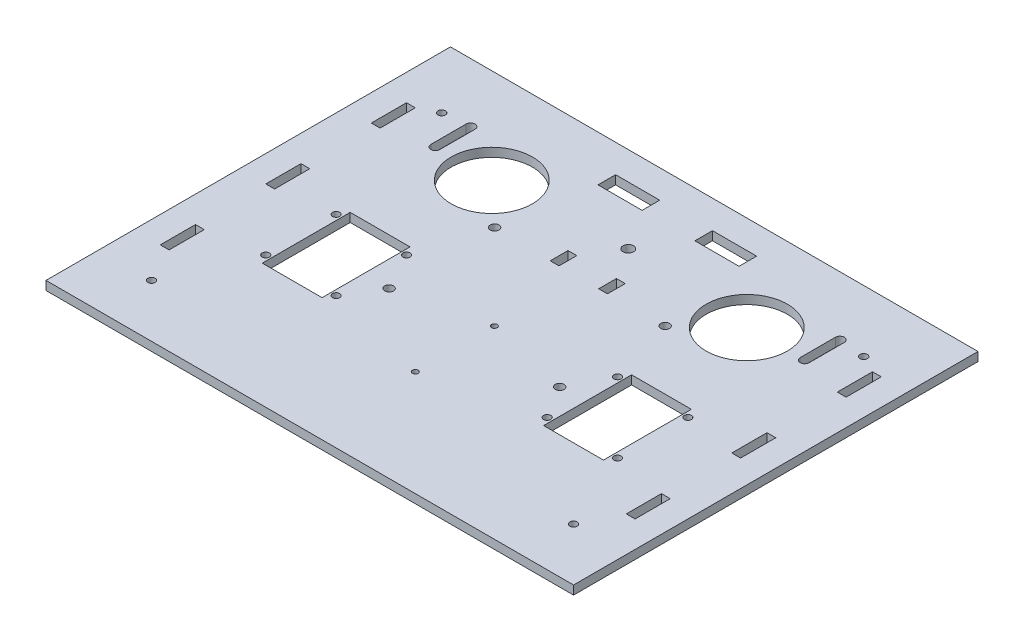
SolidWorks part; units mm, degrees
ref_plane "前基準面" through (0, 0, 0) normal (0, 0, 1) x (1, 0, 0)
ref_plane "上基準面" through (0, 0, 0) normal (0, 1, 0) x (1, 0, 0)
ref_plane "右基準面" through (0, 0, 0) normal (1, 0, 0) x (0, 0, -1)
sketch "草圖1" plane through (0, 0, 0) normal (0, 1, 0) x (1, 0, 0)
  line L0 (-130, 90) -> (130, 90) construction
  line L1 (-150, 100) -> (150, 100) construction
  line L2 (-150, 100) -> (-150, -100)
  line L3 (-150, -100) -> (150, -100) construction
  line L5 (0, 100) -> (0, -100) construction
  line L8 (-130, 100) -> (-110, 100) construction
  line L9 (-150, 100) -> (-150, -100) construction
  line L16 (-130, 100) -> (-130, -100) construction
  line L17 (-130, -100) -> (-110, -100) construction
  line L23 (-150, -100) -> (150, -100) construction
  line L26 (-150, -100) -> (-150, -120)
  line L29 (-150, -120) -> (150, -120)
  line L32 (150, -100) -> (150, -120)
  line L35 (-110, 100) -> (-110, -100) construction
  line L38 (-110, 100) -> (110, 100) construction
  line L41 (-110, 100) -> (-110, 80) construction
  line L50 (-110, 80) -> (110, 80) construction
  line L59 (110, 100) -> (110, 80) construction
  line L65 (-150, -100) -> (150, -100) construction
  line L68 (150, -100) -> (150, 100)
  line L70 (-150, 100) -> (150, 100) construction
  line L73 (-150, 100) -> (-150, 110)
  line L77 (110, 100) -> (130, 100) construction
  line L80 (110, 100) -> (110, -100) construction
  line L83 (110, -100) -> (130, -100) construction
  line L86 (130, 100) -> (130, -100) construction
  line L89 (110, -100) -> (-110, -100) construction
  line L92 (110, -100) -> (110, -80) construction
  line L93 (-150, 100) -> (150, 100) construction
  line L97 (-150, 110) -> (150, 110)
  line L98 (150, 100) -> (150, 110)
  line L108 (110, -80) -> (-110, -80) construction
  line L109 (-110, -100) -> (-110, -80) construction
  line L110 (130, -70) -> (135, -70)
  line L111 (-120, 100) -> (-120, -100) construction
  line L112 (-130, -90) -> (130, -90) construction
  line L113 (120, -100) -> (120, 100) construction
  line L114 (-130, 70) -> (-135, 70)
  line L115 (-130, 70) -> (-130, 50)
  line L116 (-130, 50) -> (-135, 50)
  line L117 (-135, 70) -> (-135, 50)
  line L118 (-130, 10) -> (-135, 10)
  line L119 (-130, 10) -> (-130, -10)
  line L120 (-130, -10) -> (-135, -10)
  line L121 (-135, 10) -> (-135, -10)
  line L122 (-130, -50) -> (-135, -50)
  line L123 (-130, -50) -> (-130, -70)
  line L124 (-130, -70) -> (-135, -70)
  line L125 (-135, -50) -> (-135, -70)
  line L126 (135, -50) -> (135, -70)
  line L127 (130, -50) -> (135, -50)
  line L128 (130, -50) -> (130, -70)
  line L129 (130, -10) -> (135, -10)
  line L130 (135, 10) -> (135, -10)
  line L131 (130, 10) -> (135, 10)
  line L132 (130, 10) -> (130, -10)
  line L133 (130, 50) -> (135, 50)
  line L134 (135, 70) -> (135, 50)
  line L135 (130, 70) -> (135, 70)
  line L136 (130, 70) -> (130, 50)
  circle A73 centre (-120, 75) radius 2.1
  circle A74 centre (120, 75) radius 2.1
  circle A75 centre (120, -90) radius 2.1
  circle A76 centre (-120, -90) radius 2.1
  point P6 (0, 0)
  point P9 (0, -80)
  point P23 (0, 0)
  point P24 (-140, 64.2857)
  point P44 (0, 0)
  point P47 (-140, 38.5714)
  point P54 (-140, 12.8571)
  point P61 (-140, -12.8571)
  point P71 (-140, -38.5714)
  point P78 (-140, -64.2857)
  dimension "D3" = 300
  dimension "D5" = 20
  dimension "D8" = 220
  dimension "D13" = 4.2
  dimension "D14" = 20
  dimension "D2" = 200
  dimension "D4" = 20
  dimension "D6" = 20
  dimension "D7" = 20
  dimension "D9" = 10
  dimension "D10" = 10
  dimension "D11" = 10
  dimension "D12" = 10
  dimension "D15" = 20
  dimension "D16" = 20
  dimension "D18" = 5
  dimension "D19" = 40
  dimension "D20" = 40
  dimension "D21" = 30
  dimension "D23" = 20
  dimension "D22" = 25
  dimension "D24" = 10
extrude "填料-伸長1" add sketch "草圖1" along normal blind 5
sketch "草圖2" plane through (0, 5, 0) normal (0, 1, 0) x (1, 0, 0)
  line L0 (0, 116.4556) -> (0, -113.9778) construction
  line L1 (115, 56) -> (30, 56) construction
  line L2 (-72.5, 98.5) -> (-72.5, 13.5) construction
  line L3 (-115, 56) -> (-30, 56) construction
  line L4 (72.5, 98.5) -> (72.5, 13.5) construction
  line L10 (7.5, -53.8861) -> (-7.5, -53.8861) construction
  line L15 (7.5, -53.8861) -> (7.5, 16.1139) construction
  line L16 (7.5, 16.1139) -> (-7.5, 16.1139) construction
  line L17 (-7.5, -53.8861) -> (-7.5, 16.1139) construction
  line L20 (-7.5, 16.1139) -> (7.5, 16.1139) construction
  line L35 (-110, 100) -> (-110, -100) construction
  line L36 (36, -46.3861) -> (-36, -46.3861) construction
  line L37 (36, -46.3861) -> (36, 63.6139) construction
  line L38 (36, 63.6139) -> (-36, 63.6139) construction
  line L39 (-36, -46.3861) -> (-36, 63.6139) construction
  line L40 (-105, 0) -> (-55, 0) construction
  line L41 (-105, 0) -> (-105, -50) construction
  line L42 (-55, 0) -> (-55, -50) construction
  line L43 (-97, 0) -> (-63, 0)
  line L46 (-97, 0) -> (-97, -50)
  line L49 (-97, -50) -> (-63, -50)
  line L60 (-7.5, -6.3861) -> (7.5, -6.3861)
  line L61 (-7.5, -6.3861) -> (-7.5, -31.3861)
  line L62 (-7.5, -31.3861) -> (7.5, -31.3861)
  line L63 (7.5, -6.3861) -> (7.5, -31.3861)
  line L64 (-63, 0) -> (-63, -50)
  line L67 (-105, -50) -> (-55, -50) construction
  line L72 (-150, 100) -> (150, 100) construction
  line L73 (-150, -100) -> (150, -100) construction
  line L74 (97, 0) -> (97, -50)
  line L75 (240, -51.3861) -> (-240, -51.3861) construction
  line L76 (240, -51.3861) -> (240, 28.6139) construction
  line L78 (-240, -51.3861) -> (-240, 28.6139) construction
  line L83 (0, -40.4951) -> (0, 39.5049) construction
  line L84 (-150, 100) -> (150, 100)
  line L85 (97, -50) -> (63, -50)
  line L86 (63, 0) -> (63, -50)
  line L87 (97, 0) -> (63, 0)
  line L88 (-7.5, -46.3861) -> (-7.5, -71.3861)
  line L89 (-7.5, -46.3861) -> (7.5, -46.3861)
  line L90 (7.5, -46.3861) -> (7.5, -71.3861)
  line L91 (-7.5, -71.3861) -> (7.5, -71.3861)
  line L92 (240, 28.6139) -> (-240, 28.6139) construction
  circle A0 centre (-72.5, 56) radius 42.5
  circle A1 centre (-72.5, 56) radius 22.1
  circle A2 centre (-87, 56) radius 2
  circle A3 centre (-58, 56) radius 2
  circle A4 centre (58, 56) radius 2
  circle A5 centre (87, 56) radius 2
  circle A6 centre (72.5, 56) radius 22.1
  circle A7 centre (72.5, 56) radius 42.5
  circle A11 centre (0, -41.3861) radius 1.25 construction
  circle A12 centre (0, 28.6139) radius 35 construction
  circle A13 centre (0, 3.6139) radius 1.25 construction
  circle A28 centre (60, -45) radius 2.05
  circle A36 centre (-100, -5) radius 2.05
  circle A37 centre (-60, -5) radius 2.05
  circle A38 centre (-100, -45) radius 2.05
  circle A39 centre (-60, -45) radius 2.05
  circle A40 centre (100, -45) radius 2.05
  circle A41 centre (60, -5) radius 2.05
  circle A42 centre (100, -5) radius 2.05
  circle A43 centre (0, -11.3861) radius 35 construction
  point P29 (0, 63.6139)
  point P46 (-7.5, -18.8861)
  point P57 (-7.5, -18.8861)
  point P68 (-36, -98.5061)
  point P69 (0, 53.9014)
  point P85 (-96.5, 66.7857)
  point P90 (-141.5, 66.7857)
  point P91 (-140, 13.2857)
  point P92 (-140, 68.2857)
  point P116 (0, -53.8861)
  point P142 (0, -51.3861)
  point P143 (0, 53.9014)
  dimension "D1" = 85
  dimension "D2" = 44.2
  dimension "D4" = 4
  dimension "D8" = 72
  dimension "D10" = 44
  dimension "D7" = 2
  dimension "D16" = 70
  dimension "D13" = 2.5
  dimension "D17" = 2
  dimension "D24" = 45
  dimension "D25" = 4.1
  dimension "D33" = 8
  dimension "D3" = 29
  dimension "D5" = 60
  dimension "D6" = 12.5
  dimension "D9" = 25
  dimension "D11" = 70
  dimension "D12" = 110
  dimension "D14" = 5
  dimension "D15" = 5
  dimension "D18" = 40
  dimension "D19" = 40
  dimension "D20" = 45
  dimension "D21" = 34
  dimension "D23" = 50
  dimension "D26" = 2
  dimension "D27" = 40
  dimension "D29" = 55
  dimension "D30" = 50
  dimension "D31" = 15
  dimension "D32" = 40
  dimension "D40" = 5
  dimension "D41" = 5
  dimension "D42" = 50
  dimension "D43" = 80
  dimension "D44" = 480
sketch "草圖3" plane through (0, 5, 0) normal (0, 1, 0) x (1, 0, 0)
  line L0 (0, 200116.4556) -> (0, -200113.9778) construction
  line L1 (0, 200116.4556) -> (0, -200113.9778) construction
  line L2 (0, 100) -> (0, -100) construction
  line L3 (-41, 43.6139) -> (-56, 43.6139) construction
  line L4 (-41, 43.6139) -> (-41, 23.6139) construction
  line L5 (-41, 23.6139) -> (-56, 23.6139) construction
  line L6 (-56, 43.6139) -> (-56, 23.6139) construction
  line L7 (0, 0) -> (0, 42.1207) construction
  line L8 (41, 23.6139) -> (56, 23.6139) construction
  line L9 (-7.5, -53.8861) -> (-7.5, 16.1139) construction
  line L10 (7.5, 16.1139) -> (-7.5, 16.1139) construction
  line L11 (7.5, 16.1139) -> (7.5, 26.1139) construction
  line L12 (7.5, 26.1139) -> (-7.5, 26.1139) construction
  line L13 (-7.5, 16.1139) -> (-7.5, 26.1139) construction
  line L14 (41, 43.6139) -> (41, 23.6139) construction
  line L15 (56, 43.6139) -> (56, 23.6139) construction
  line L16 (41, 43.6139) -> (56, 43.6139) construction
  line L17 (-97, -50) -> (-63, -50) construction
  line L18 (-63, 0) -> (-63, -50) construction
  line L19 (-97, 0) -> (-63, 0) construction
  line L20 (-97, 0) -> (-97, -50) construction
  line L21 (-97, -50) -> (-63, -50)
  line L22 (-63, 0) -> (-63, -50)
  line L23 (-97, 0) -> (-63, 0)
  line L24 (-97, 0) -> (-97, -50)
  line L25 (97, 0) -> (97, -50)
  line L26 (97, 0) -> (63, 0)
  line L27 (63, 0) -> (63, -50)
  line L28 (97, -50) -> (63, -50)
  line L29 (36, 63.6139) -> (-36, 63.6139) construction
  line L30 (-11.275, 68.1139) -> (11.275, 68.1139) construction
  line L31 (-11.275, 68.1139) -> (-11.275, 31.1139) construction
  line L32 (-11.275, 31.1139) -> (11.275, 31.1139) construction
  line L33 (11.275, 68.1139) -> (11.275, 31.1139) construction
  line L34 (-11.275, 43.1139) -> (-16.275, 43.1139)
  line L35 (-11.275, 43.1139) -> (-11.275, 33.0139)
  line L36 (-11.275, 33.0139) -> (-16.275, 33.0139)
  line L37 (-16.275, 43.1139) -> (-16.275, 33.0139)
  line L38 (11.275, 43.1139) -> (16.275, 43.1139)
  line L39 (11.275, 43.1139) -> (11.275, 33.0139)
  line L40 (11.275, 33.0139) -> (16.275, 33.0139)
  line L41 (16.275, 43.1139) -> (16.275, 33.0139)
  line L42 (-150, -120) -> (150, -120) construction
  circle A1 centre (0, -60) radius 1.6
  circle A3 centre (0, -15) radius 1.6
  circle A10 centre (-48.5, 33.6139) radius 2.5
  circle A11 centre (48.5, 33.6139) radius 2.5
  circle A12 centre (48.5, -26.3861) radius 2.5
  circle A13 centre (-48.5, -26.3861) radius 2.5
  circle A14 centre (-72.5, 56) radius 22.1 construction
  circle A15 centre (-72.5, 56) radius 22.1 construction
  circle A16 centre (72.5, 56) radius 22.1 construction
  circle A17 centre (72.5, 56) radius 22.1 construction
  circle A18 centre (-72.5, 56) radius 23.1
  circle A19 centre (72.5, 56) radius 23.1
  circle A20 centre (0, 61.1139) radius 3
  circle A21 centre (0, 21.1139) radius 2 construction
  circle A22 centre (-100, -45) radius 2.05 construction
  circle A23 centre (-60, -45) radius 2.05 construction
  circle A24 centre (-60, -5) radius 2.05 construction
  circle A25 centre (-100, -5) radius 2.05 construction
  circle A26 centre (-100, -45) radius 2.05
  circle A27 centre (-60, -45) radius 2.05
  circle A28 centre (-60, -5) radius 2.05
  circle A29 centre (-100, -5) radius 2.05
  circle A30 centre (100, -5) radius 2.05
  circle A31 centre (60, -5) radius 2.05
  circle A32 centre (60, -45) radius 2.05
  circle A33 centre (100, -45) radius 2.05
  point P1 (0, -23.4332)
  point P4 (0, -69.4079)
  point P22 (-72.5, 65)
  point P29 (-56, 33.6139)
  point P32 (-48.5, 23.6139)
  point P41 (0, 21.1139)
  point P62 (-7.5, 21.1139)
  point P64 (0, 68.1139)
  point P97 (0, 0)
  point P98 (0, 0)
  point P99 (0, -62.9584)
  dimension "D2" = 5
  dimension "D8" = 6
  dimension "D11" = 4
  dimension "D7" = 1
  dimension "D20" = 1
  dimension "D21" = 3.2
  dimension "D3" = 15
  dimension "D4" = 20
  dimension "D5" = 2
  dimension "D6" = 60
  dimension "D9" = 40
  dimension "D10" = 10
  dimension "D12" = 112
  dimension "D13" = 20
  dimension "D14" = 22.55
  dimension "D15" = 37
  dimension "D16" = 7
  dimension "D17" = 5
  dimension "D18" = 10.1
  dimension "D19" = 25
  dimension "D22" = 45
  dimension "D23" = 60
extrude "除料-伸長1" cut sketch "草圖3" against normal through all
sketch "草圖5" plane through (0, 5, 0) normal (0, 1, 0) x (1, 0, 0)
  line L0 (-150, 84) -> (150, 84) construction
  line L1 (-150, 110) -> (-150, -120) construction
  line L2 (150, -120) -> (150, 110) construction
  line L3 (-150, 94) -> (150, 94) construction
  line L5 (0, 81.1139) -> (0, 61.1139) construction
  line L8 (-0.85, 61.1139) -> (0.85, 61.1139) construction
  line L9 (-0.85, 63.0139) -> (0.85, 63.0139) construction
  line L10 (-0.85, 59.2139) -> (0.85, 59.2139) construction
  line L11 (5.05, 81.1139) -> (5.05, 61.1139) construction
  line L12 (-5.05, 81.1139) -> (-5.05, 61.1139) construction
  line L13 (0, 0) -> (0, 152.3042) construction
  line L14 (-15, 94) -> (15, 94) construction
  line L15 (-15, 94) -> (-15, 84) construction
  line L16 (-15, 84) -> (15, 84) construction
  line L17 (15, 94) -> (15, 84) construction
  line L18 (15, 84) -> (40.1, 84)
  line L19 (-15, 94) -> (-40.1, 94)
  line L20 (-15, 94) -> (-15, 84)
  line L21 (-15, 84) -> (-40.1, 84)
  line L22 (-40.1, 94) -> (-40.1, 84)
  line L23 (40.1, 94) -> (40.1, 84)
  line L24 (15, 94) -> (40.1, 94)
  line L25 (15, 94) -> (15, 84)
  line L26 (-150, 100) -> (150, 100) construction
  line L27 (-150, 100) -> (150, 100) construction
  line L28 (-105, 76.45) -> (-105, 56.45) construction
  line L29 (-102.45, 76.45) -> (-102.45, 56.45)
  line L30 (-107.55, 76.45) -> (-107.55, 56.45)
  line L31 (-113, 66.45) -> (-97, 66.45) construction
  line L32 (-130, 70) -> (-110, 70) construction
  line L33 (-130, 70) -> (-130, 35.4173) construction
  line L34 (-130, 35.4173) -> (-110, 35.4173) construction
  line L35 (-110, 70) -> (-110, 35.4173) construction
  line L36 (105, 76.45) -> (105, 56.45) construction
  line L37 (102.45, 76.45) -> (102.45, 56.45)
  line L38 (107.55, 76.45) -> (107.55, 56.45)
  circle A0 centre (0, 61.1139) radius 3 construction
  circle A1 centre (0, 61.1139) radius 3 construction
  circle A4 centre (0, 81.1139) radius 2.05 construction
  arc A5 (-0.85, 63.0139) -> (-0.85, 59.2139) centre (-0.85, 61.1139) ccw construction
  arc A6 (0.85, 59.2139) -> (0.85, 63.0139) centre (0.85, 61.1139) ccw construction
  arc A7 (5.05, 81.1139) -> (-5.05, 81.1139) centre (0, 81.1139) ccw construction
  arc A8 (-5.05, 61.1139) -> (5.05, 61.1139) centre (0, 61.1139) ccw construction
  arc A9 (-102.45, 76.45) -> (-107.55, 76.45) centre (-105, 76.45) ccw
  arc A10 (-107.55, 56.45) -> (-102.45, 56.45) centre (-105, 56.45) ccw
  arc A11 (102.45, 76.45) -> (107.55, 76.45) centre (105, 76.45) cw
  arc A12 (107.55, 56.45) -> (102.45, 56.45) centre (105, 56.45) cw
  point P3 (0, 71.1139)
  point P18 (0, 56.0639)
  point P19 (0, 86.1639)
  point P24 (0, 61.1139)
  point P29 (-2.75, 61.1139)
  point P30 (2.75, 61.1139)
  point P38 (0, 94)
  point P44 (-105, 66.45)
  point P51 (-105, 79)
  point P56 (-85.2761, 68.45)
  point P60 (-105, 66.45)
  point P61 (0, 0)
  point P64 (105, 66.45)
  dimension "D1" = 20
  dimension "D2" = 4.1
  dimension "D3" = 10
  dimension "D4" = 16
  dimension "D5" = 30.1
  dimension "D6" = 5.5
  dimension "D7" = 3.8
  dimension "D8" = 30
  dimension "D9" = 25.1
  dimension "D10" = 5.1
  dimension "D11" = 20
  dimension "D12" = 5
  dimension "D13" = 20
  dimension "D14" = 5
  dimension "D15" = 16
extrude "除料-伸長5" cut sketch "草圖5" against normal through all
